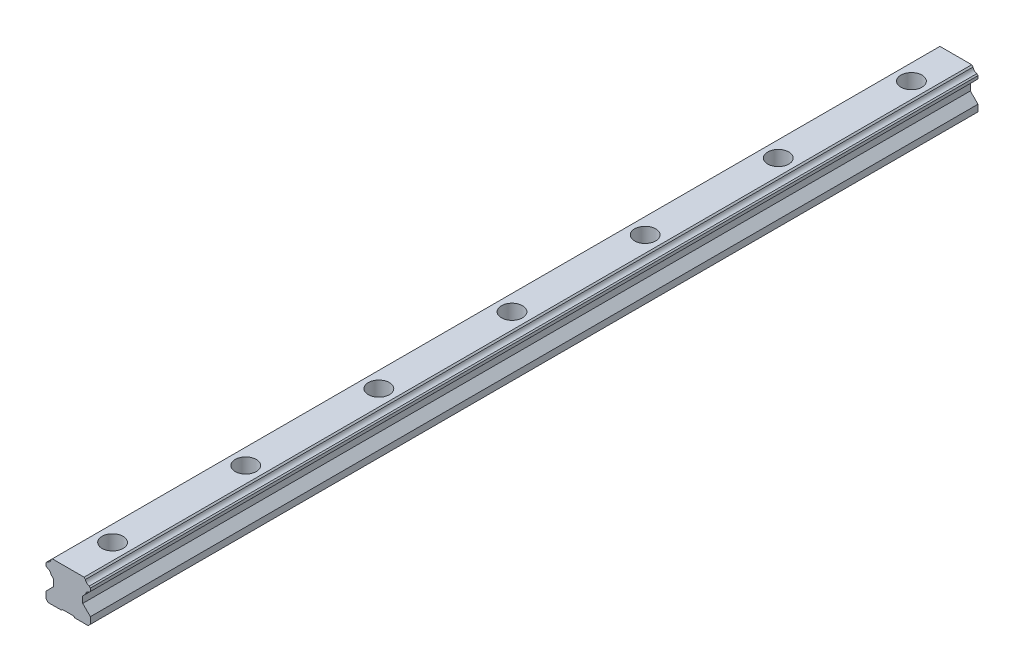
SolidWorks part; units mm, degrees
material "Plain Carbon Steel"
ref_plane "Front Plane" through (0, 0, 0) normal (0, 0, 1) x (1, 0, 0)
ref_plane "Top Plane" through (0, 0, 0) normal (0, 1, 0) x (1, 0, 0)
ref_plane "Right Plane" through (0, 0, 0) normal (1, 0, 0) x (0, 0, -1)
sketch "Sketch1" plane through (0, 0, 0) normal (0, 0, 1) x (1, 0, 0)
  line L0 (-10, -10.4945) -> (-10, -13.4946)
  line L1 (-10, -13.4946) -> (-9, -14.4946)
  line L2 (-9, -14.4946) -> (-3, -14.4946)
  line L3 (-3, -14.4946) -> (-2.5, -13.9946)
  line L4 (-2.5, -13.9946) -> (2.5, -13.9946)
  line L5 (6.55, -7.0447) -> (10, -10.4945)
  line L6 (6.55, -4.1154) -> (6.55, -7.0447)
  line L7 (7.7679, -2.8995) -> (6.55, -4.1154)
  line L8 (10, -0.6654) -> (9.4727, -1.1802)
  line L9 (10, 0.6654) -> (10, -0.6654)
  line L10 (9.4727, 1.1928) -> (10, 0.6654)
  line L11 (7.16, 3.5054) -> (7.7679, 2.8975)
  line L12 (3, -14.4946) -> (2.5, -13.9946)
  line L13 (9, -14.4946) -> (3, -14.4946)
  line L14 (10, -13.4946) -> (9, -14.4946)
  line L15 (10, -10.4945) -> (10, -13.4946)
  line L16 (7.16, 3.5054) -> (-7.16, 3.5054)
  line L17 (-7.16, 3.5054) -> (-7.7679, 2.8975)
  line L18 (-9.4727, 1.1928) -> (-10, 0.6654)
  line L19 (-10, 0.6654) -> (-10, -0.6654)
  line L20 (-10, -0.6654) -> (-9.4727, -1.1802)
  line L21 (-7.7679, -2.8995) -> (-6.55, -4.1154)
  line L22 (-6.55, -4.1154) -> (-6.55, -7.0447)
  line L23 (-6.55, -7.0447) -> (-10, -10.4945)
  line L24 (0, -14.4946) -> (0, -13.9946) construction
  line L25 (0, -13.9946) -> (0, 3.5054) construction
  line L26 (55, 0) -> (-55, 0) construction
  arc A0 (9.4727, -1.1802) -> (7.7679, -2.8995) centre (9.8039, -3.2134) ccw
  arc A1 (7.7679, 2.8975) -> (9.4727, 1.1928) centre (9.8015, 3.2263) ccw
  arc A2 (-7.7679, 2.8975) -> (-9.4727, 1.1928) centre (-9.8015, 3.2263) cw
  arc A3 (-9.4727, -1.1802) -> (-7.7679, -2.8995) centre (-9.8039, -3.2134) cw
  point P38 (10, 0)
  dimension "D17" = 2.06
  dimension "D1" = 20
  dimension "D2" = 1
  dimension "D3" = 1
  dimension "D4" = 0.5
  dimension "D5" = 0.5
  dimension "D6" = 6
  dimension "D7" = 18
  dimension "D8" = 4.0001
  dimension "D9" = 10.55
  dimension "D10" = 13.1001
  dimension "D11" = 15.5359
  dimension "D12" = 0.6079
  dimension "D13" = 0.6079
  dimension "D14" = 17.5
  dimension "D15" = 0.5273
  dimension "D16" = 0.5273
  dimension "D18" = 1.2159
  dimension "D19" = 0.5148
  dimension "D20" = 6.4049
  dimension "D21" = 2.84
  dimension "D22" = 4.1708
extrude "Boss-Extrude1" add sketch "Sketch1" against normal mid plane 400
sketch "Sketch2" plane through (0, 0, 0) normal (1, 0, 0) x (0, 0, -1)
  line L0 (-180, 3.5054) -> (-180, -14.4946)
  line L1 (200, 3.5054) -> (-200, 3.5054) construction
  line L2 (200, -14.4946) -> (-200, -14.4946) construction
  line L3 (-180, -14.4946) -> (-183, -14.4946)
  line L4 (-183, -14.4946) -> (-183, -4.9946)
  line L5 (-183, -4.9946) -> (-184.75, -4.9946)
  line L6 (-184.75, -4.9946) -> (-184.75, 3.5054)
  line L7 (-184.75, 3.5054) -> (-180, 3.5054)
  line L8 (-200, -7.0447) -> (-200, -4.1154) construction
  point P12 (-200, -5.58)
  dimension "D1" = 3
  dimension "D2" = 4.75
  dimension "D3" = 8.5
  dimension "D4" = 20
revolve "Cut-Revolve1" cut sketch "Sketch2" angle 360 about L0
pattern_linear "LPattern1" count 7 spacing 60 along (0, 0, -1) of "Cut-Revolve1"
equation "\"Length\" = 400"
equation "\"Pitch\"= 60mm"
equation "\"Holes\"= int ( ( \"Length\" + \"Pitch\" / 2 ) / \"Pitch\" )"
equation "\"EndSpacing\"= ( \"Length\" - \"Pitch\" * ( \"Holes\" - 1 ) ) / 2"
equation "\"D4@Sketch2\"=\"EndSpacing\""
equation "\"D3@LPattern1\"=\"Pitch\""
equation "\"D1@LPattern1\"=\"Holes\""
equation "\"D1@Boss-Extrude1\"=\"Length\""
